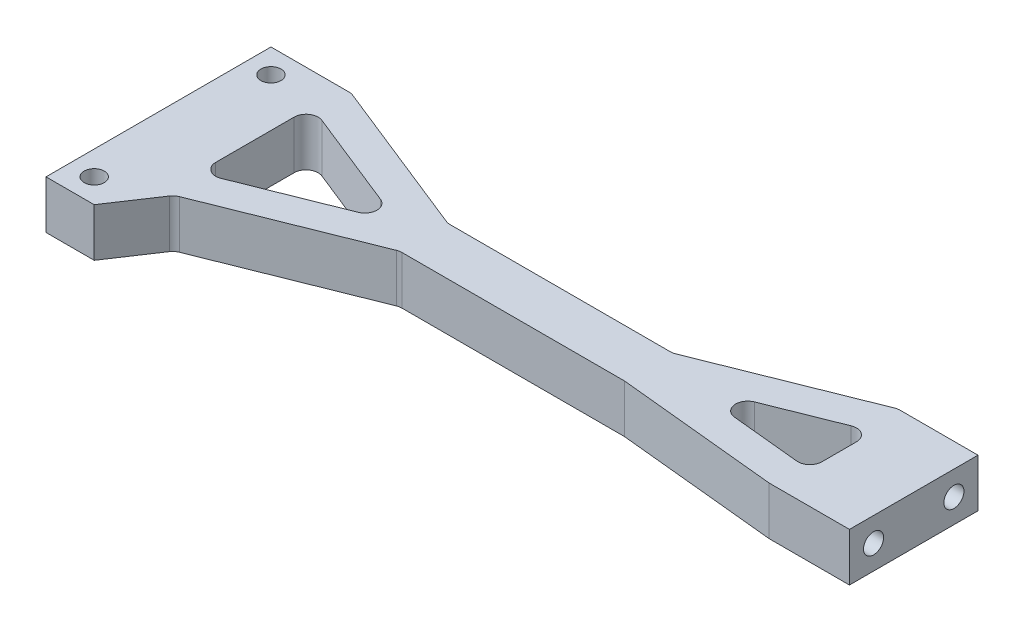
SolidWorks part; units mm, degrees
material "1060 Alloy"
ref_plane "Front Plane" through (0, 0, 0) normal (0, 0, 1) x (1, 0, 0)
ref_plane "Top Plane" through (0, 0, 0) normal (0, 1, 0) x (1, 0, 0)
ref_plane "Right Plane" through (0, 0, 0) normal (1, 0, 0) x (0, 0, -1)
sketch "Sketch2" plane through (0, 0, 0) normal (0, 1, 0) x (1, 0, 0)
  line L0 (58, -8) -> (78, 0)
  line L1 (88, -16) -> (78, -16)
  line L2 (58, -14) -> (30, -14)
  line L3 (10, -22) -> (6, -28)
  line L4 (6, -28) -> (0, -28)
  line L5 (0, -28) -> (0, 0)
  line L6 (88, -16) -> (88, 0)
  line L7 (88, 0) -> (78, 0)
  line L8 (9, -3.9081) -> (26.7297, -11)
  line L9 (58, -8) -> (30, -8)
  line L10 (78, -16) -> (58, -14)
  line L11 (10, 0) -> (0, 0)
  line L12 (30, -14) -> (10, -22)
  line L13 (30, -8) -> (10, 0)
  line L14 (26.7297, -11) -> (9, -18.0919)
  line L15 (9, -18.0919) -> (9, -3.9081)
  line L17 (62.6562, -10.4457) -> (79, -12.08)
  line L18 (79, -12.08) -> (79, -3.9081)
  line L19 (79, -3.9081) -> (62.6562, -10.4457)
  dimension "D1" = 6
  dimension "D2" = 88
  dimension "D3" = 6
  dimension "D4" = 10
  dimension "D5" = 28
  dimension "D6" = 10
  dimension "D7" = 20
  dimension "D8" = 20
  dimension "D9" = 16
  dimension "D10" = 4
  dimension "D11" = 4
  dimension "D12" = 4
  dimension "D13" = 4
  dimension "D14" = 8
  dimension "D15" = 9
  dimension "D16" = 9
  dimension "D17" = 8
extrude "Boss-Extrude1" add sketch "Sketch2" along normal blind 6
hole_wizard "Tap Drill for M3 Tap3" positions "Sketch8" profile "Sketch7" hole size "M3" standard "ISO"
sketch "Sketch8" plane through (0, 6, 0) normal (0, 1, 0) x (1, 0, 0)
  line L2 (0, -28) -> (6, -28) construction
  line L4 (0, 0) -> (0, -28) construction
  line L6 (10, 0) -> (0, 0) construction
  point P0 (3, -3)
  point P2 (3, -25)
  dimension "D1" = 3
  dimension "D2" = 3
  dimension "D3" = 3
  dimension "D4" = 3
sketch "Sketch7" plane through (3, 6, 3) normal (1, 0, 0) x (0, 0, 1)
  line L0 (0, 0) -> (0, 10.7511)
  line L1 (0, 10.7511) -> (1.25, 10)
  line L2 (1.25, 10) -> (1.25, 0)
  line L5 (1.25, 0) -> (0, 0)
  line L10 (0, 10.7511) -> (-1.25, 10) construction
  line L11 (0, -6.35) -> (0, 107.95) construction
  dimension "Hole Dia." = 2.5
  dimension "Hole Depth" = 10
  dimension "Drill Angle" = 118
hole_wizard "Tap Drill for M3 Tap2" positions "Sketch6" profile "Sketch5" hole size "M3" standard "ISO"
sketch "Sketch6" plane through (88, 0.7792, 7.6405) normal (1, 0, 0) x (0, 0, -1)
  line L4 (-8.3595, -0.7792) -> (7.6405, -0.7792) construction
  line L5 (7.6405, 5.2208) -> (7.6405, -0.7792) construction
  point P0 (-5.3595, 2.2208)
  point P2 (4.6405, 2.2208)
  dimension "D1" = 3
  dimension "D2" = 3
  dimension "D3" = 10
sketch "Sketch5" plane through (88, 3, 13) normal (0, 1, 0) x (0, 0, -1)
  line L0 (0, 0) -> (0, 8.7511)
  line L1 (0, 8.7511) -> (1.25, 8)
  line L2 (1.25, 8) -> (1.25, 0)
  line L5 (1.25, 0) -> (0, 0)
  line L10 (0, 8.7511) -> (-1.25, 8) construction
  line L11 (0, -6.35) -> (0, 107.95) construction
  dimension "Hole Dia." = 2.5
  dimension "Hole Depth" = 8
  dimension "Drill Angle" = 118
hole_wizard "Tap Drill for M3 Tap1" positions "Sketch4" profile "Sketch3" hole size "M3" standard "ISO"
sketch "Sketch4" plane through (0, 0, 0) normal (-1, 0, 0) x (0, 0, 1)
  line L0 (0, 0) -> (28, 0) construction
  line L2 (0, 6) -> (0, 0) construction
  point P0 (8, 3)
  point P2 (18, 3)
  dimension "D1" = 3
  dimension "D2" = 8
  dimension "D3" = 10
sketch "Sketch3" plane through (0, 3, 8) normal (0, 1, 0) x (0, 0, 1)
  line L0 (0, 0) -> (0, 8.7511)
  line L1 (0, 8.7511) -> (1.25, 8)
  line L2 (1.25, 8) -> (1.25, 0)
  line L5 (1.25, 0) -> (0, 0)
  line L10 (0, 8.7511) -> (-1.25, 8) construction
  line L11 (0, -6.35) -> (0, 107.95) construction
  dimension "Hole Dia." = 2.5
  dimension "Hole Depth" = 8
  dimension "Drill Angle" = 118
fillet "Fillet1" radius 1.5 12 edges at (78, 3, 0) (58, 3, 8) (62.6562, 3, 10.4457) (79, 3, 12.08) (79, 3, 3.9081) (30, 3, 14) (10, 3, 22) (30, 3, 8) (10, 3, 0) (9, 3, 18.0919) (26.7297, 3, 11) (9, 3, 3.9081)
